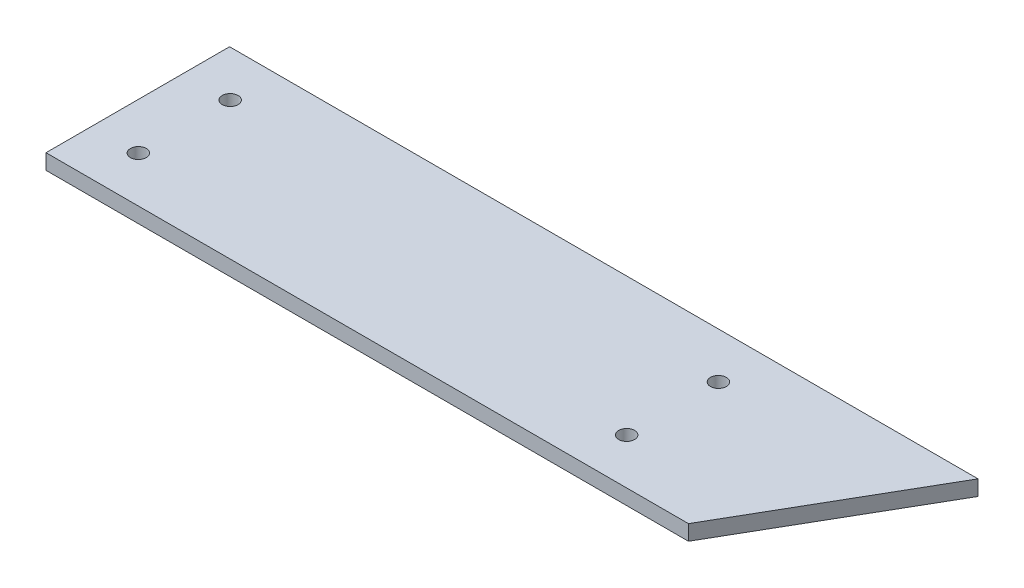
SolidWorks part; units mm, degrees
ref_plane "Front Plane" through (0, 0, 0) normal (0, 0, 1) x (1, 0, 0)
ref_plane "Top Plane" through (0, 0, 0) normal (0, 1, 0) x (1, 0, 0)
ref_plane "Right Plane" through (0, 0, 0) normal (1, 0, 0) x (0, 0, -1)
sketch "Sketch1" plane through (0, 0, 0) normal (0, 1, 0) x (1, 0, 0)
  line L0 (66.675, 19.05) -> (88.672, 19.05)
  line L1 (66.675, -19.05) -> (-66.675, -19.05)
  line L2 (66.675, -19.05) -> (66.675, 19.05) construction
  line L3 (66.675, 19.05) -> (-66.675, 19.05)
  line L4 (-66.675, -19.05) -> (-66.675, 19.05)
  line L5 (66.675, -19.05) -> (-66.675, 19.05) construction
  line L6 (66.675, 19.05) -> (-66.675, -19.05) construction
  line L7 (88.672, 19.05) -> (66.675, -19.05)
  point P0 (0, 0)
  dimension "D1" = 133.35
  dimension "D2" = 38.1
  dimension "D3" = 60
extrude "Boss-Extrude1" add sketch "Sketch1" along normal mid plane 3.175
sketch "Sketch2" plane through (0, 1.5875, 0) normal (0, 1, 0) x (1, 0, 0)
  line L0 (-66.675, 19.05) -> (-66.675, -19.05) construction
  line L1 (44.323, -9.525) -> (-57.023, -9.525) construction
  line L2 (44.323, -9.525) -> (44.323, 9.525) construction
  line L3 (44.323, 9.525) -> (-57.023, 9.525) construction
  line L4 (-57.023, -9.525) -> (-57.023, 9.525) construction
  circle A0 centre (-57.023, 9.525) radius 1.651
  circle A1 centre (-57.023, -9.525) radius 1.651
  circle A2 centre (44.323, -9.525) radius 1.651
  circle A3 centre (44.323, 9.525) radius 1.651
  point P0 (0, 0)
  dimension "D3" = 3.302
  dimension "D1" = 9.652
  dimension "D2" = 19.05
  dimension "D4" = 101.346
extrude "Cut-Extrude1" cut sketch "Sketch2" against normal up to surface (3.175 mm away) up to face at (5.4993, -1.5875, 0)
